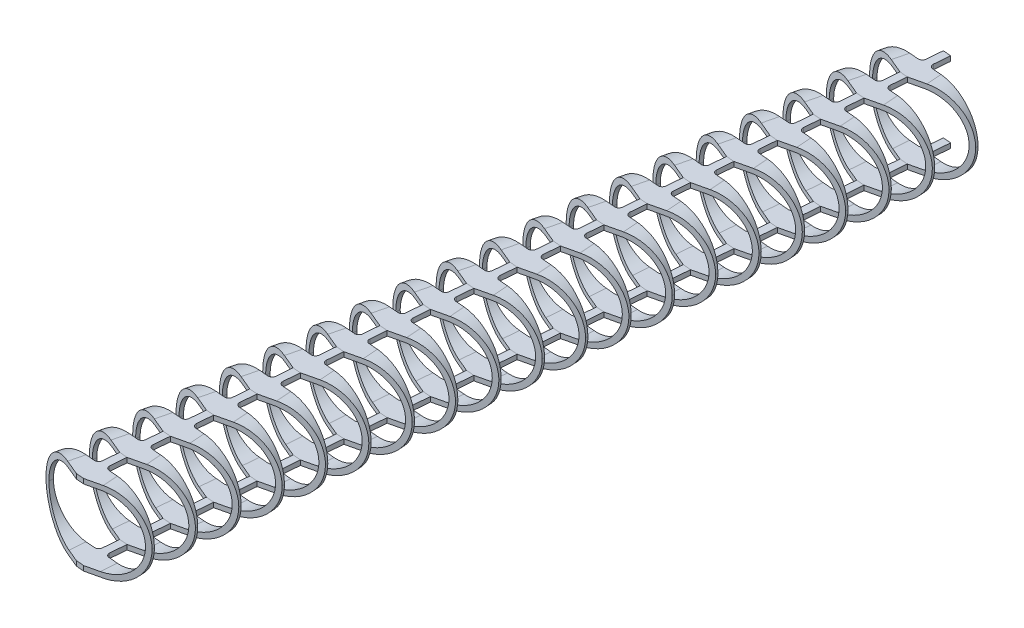
SolidWorks part; units mm, degrees
material "Rubber"
ref_plane "Front Plane" through (0, 0, 0) normal (0, 0, 1) x (1, 0, 0)
ref_plane "Top Plane" through (0, 0, 0) normal (0, 1, 0) x (1, 0, 0)
ref_plane "Right Plane" through (0, 0, 0) normal (1, 0, 0) x (0, 0, -1)
sketch "Sketch1" plane through (0, 0, 0) normal (0, 1, 0) x (1, 0, 0)
  line L1 (41.8892, -69.2126) -> (74.5712, -31.3723) construction
  line L2 (74.5712, -31.3723) -> (78.7696, 18.4511) construction
  line L3 (78.7696, 18.4511) -> (52.8806, 61.2268) construction
  line L4 (52.8806, 61.2268) -> (6.7931, 80.616) construction
  line L5 (6.7931, 80.616) -> (-41.8892, 69.2126) construction
  line L6 (-41.8892, 69.2126) -> (-74.5712, 31.3723) construction
  line L7 (-74.5712, 31.3723) -> (-78.7696, -18.4511) construction
  line L8 (-78.7696, -18.4511) -> (-52.8806, -61.2268) construction
  line L9 (-52.8806, -61.2268) -> (-6.7931, -80.616) construction
  line L10 (-6.7931, -80.616) -> (41.8892, -69.2126) construction
  line L11 (9.9647, -0.8397) -> (76.6704, -6.4606)
  line L12 (74.5712, -31.3723) -> (9.2175, -3.8778)
  line L13 (9.2175, -3.8778) -> (9.9647, -0.8397)
  line L18 (79.5535, -31.7922) -> (83.7519, 18.0313) construction
  line L19 (76.6704, -6.4606) -> (78.7696, 18.4511)
  line L20 (78.7696, 18.4511) -> (88.7342, 17.6114)
  line L21 (74.5712, -31.3723) -> (84.5359, -32.212)
  line L22 (86.6351, -7.3003) -> (88.7342, 17.6114)
  line L23 (84.5359, -32.212) -> (153.569, -16.0416)
  line L24 (153.569, -16.0416) -> (153.3407, -12.9213)
  line L25 (153.3407, -12.9213) -> (86.6351, -7.3003)
  line L26 (76.6704, -6.4606) -> (86.6351, -7.3003) construction
  circle A0 centre (0, 0) radius 10 construction
  circle A2 centre (0, 0) radius 76.9421 construction
  dimension "D1" = 20
  dimension "D2" = 50
  dimension "D3" = 76.9421
extrude "Boss-Extrude2" add sketch "Sketch1" along normal blind 100
fillet "Fillet1" radius 50 4 edges at (9.5911, 100, 2.3588) (9.5911, 0, 2.3588) (153.4549, 0, 14.4814) (153.4549, 100, 14.4814)
fillet "Fillet2" radius 5 2 edges at (76.6704, 50, 6.4606) (86.6351, 50, 7.3003)
sketch "Sketch8" plane through (0, 0, 0) normal (0.084, 0, -0.9965) x (-0.9965, 0, -0.084)
  line L0 (-71.9421, 100) -> (-91.9421, 100) construction
  line L1 (-81.9421, 100) -> (-81.9421, 0) construction
  line L2 (-97.9421, 94) -> (-65.9421, 94)
  line L3 (-65.9421, 6) -> (-97.9421, 6)
  line L26 (-60.6233, 94) -> (-65.9421, 94)
  line L27 (-65.9421, 94) -> (-65.9421, 6)
  line L28 (-65.9421, 6) -> (-60.6233, 6)
  line L29 (-60.6233, 94) -> (-65.9421, 94)
  line L31 (-65.9421, 6) -> (-60.6233, 6)
  line L35 (-103.2609, 6) -> (-97.9421, 6)
  line L36 (-97.9421, 6) -> (-97.9421, 94)
  line L37 (-97.9421, 94) -> (-103.2609, 94)
  line L38 (-103.2609, 6) -> (-97.9421, 6)
  line L40 (-97.9421, 94) -> (-103.2609, 94)
  spline S0 degree 3 poles (-1167.3923, 3837.039) (-480.5269, 705.4147) (-201.9731, -22.3402) (-50.5717, 7.1072) (-49.1672, 7.4506) (-46.3819, 8.2764) (-44.9956, 8.7616) (-40.9575, 10.3993) (-38.4016, 11.7367) (-34.7705, 14.1083) (-33.5942, 14.9602) (-31.3123, 16.7917) (-30.2259, 17.7559) (-27.126, 20.7889) (-25.27, 22.9968) (-22.809, 26.5942) (-22.0407, 27.8467) (-20.6474, 30.3952) (-19.3888, 32.9977) (-18.3948, 35.7064) (-17.7498, 37.7782) (-17.5516, 38.4755) (-17.1892, 39.8838) (-17.0248, 40.5962) (20.8316, 225.9233) (-1153.7583, 538.5496) (-3883.4737, 1015.3924) knots -6.495019 -6.495019 -6.495019 -6.495019 0.125 0.125 0.1875 0.1875 0.25 0.25 0.375 0.375 0.4375 0.4375 0.5 0.5 0.625 0.625 0.6875 0.6875 0.75 0.8125 0.8125 0.84375 0.84375 0.875 0.875 8.929608 8.929608 8.929608 8.929608 only from (-60.6233, 6) to (-16, 50)
  spline S1 degree 3 poles (-3850.2068, -1047.6989) (-700.7376, -359.2624) (12.651, -86.8768) (-17.1536, 60.0441) (-17.5112, 61.4461) (-18.1559, 63.5305) (-18.3896, 64.224) (-18.8905, 65.5954) (-19.1572, 66.2722) (-20.5702, 69.6118) (-21.9524, 72.1439) (-23.9915, 75.1366) (-24.4151, 75.7264) (-25.2941, 76.8884) (-25.7506, 77.4617) (-27.1543, 79.1374) (-28.1386, 80.2004) (-31.2327, 83.232) (-33.4822, 85.0448) (-36.533, 87.0442) (-37.1551, 87.4304) (-38.4097, 88.1675) (-39.044, 88.5196) (-40.9672, 89.5272) (-43.5859, 90.7414) (-46.312, 91.7003) (-48.3973, 92.3224) (-49.0993, 92.5135) (-50.517, 92.8627) (-51.2313, 93.0204) (-231.643, 128.2853) (-539.1448, -934.7881) (-1052.4637, -3766.3996) knots -6.30639 -6.30639 -6.30639 -6.30639 0.125 0.125 0.1875 0.1875 0.21875 0.21875 0.25 0.25 0.375 0.375 0.40625 0.40625 0.4375 0.4375 0.5 0.5 0.625 0.625 0.65625 0.65625 0.6875 0.6875 0.75 0.8125 0.8125 0.84375 0.84375 0.875 0.875 8.729297 8.729297 8.729297 8.729297 only from (-16, 50) to (-60.6233, 94)
  spline S2 degree 3 poles (-60.6233, 6) (-57.6977, 6) (-54.8198, 6.281) (-50.5717, 7.1072) (-49.1672, 7.4506) (-46.3819, 8.2764) (-44.9956, 8.7616) (-40.9575, 10.3993) (-38.4016, 11.7367) (-34.7705, 14.1083) (-33.5942, 14.9602) (-31.3123, 16.7917) (-30.2259, 17.7559) (-27.126, 20.7889) (-25.27, 22.9968) (-22.809, 26.5942) (-22.0407, 27.8467) (-20.6474, 30.3952) (-19.3888, 32.9977) (-18.3948, 35.7064) (-17.7498, 37.7782) (-17.5516, 38.4755) (-17.1892, 39.8838) (-17.0248, 40.5962) (-16.2933, 44.1774) (-16, 47.0732) (-16, 50) knots 0 0 0 0 0.125 0.125 0.1875 0.1875 0.25 0.25 0.375 0.375 0.4375 0.4375 0.5 0.5 0.625 0.625 0.6875 0.6875 0.75 0.8125 0.8125 0.84375 0.84375 0.875 0.875 1 1 1 1
  spline S3 degree 3 poles (-16, 50) (-16, 52.926) (-16.2931, 55.802) (-17.1536, 60.0441) (-17.5112, 61.4461) (-18.1559, 63.5305) (-18.3896, 64.224) (-18.8905, 65.5954) (-19.1572, 66.2722) (-20.5702, 69.6118) (-21.9524, 72.1439) (-23.9915, 75.1366) (-24.4151, 75.7264) (-25.2941, 76.8884) (-25.7506, 77.4617) (-27.1543, 79.1374) (-28.1386, 80.2004) (-31.2327, 83.232) (-33.4822, 85.0448) (-36.533, 87.0442) (-37.1551, 87.4304) (-38.4097, 88.1675) (-39.044, 88.5196) (-40.9672, 89.5272) (-43.5859, 90.7414) (-46.312, 91.7003) (-48.3973, 92.3224) (-49.0993, 92.5135) (-50.517, 92.8627) (-51.2313, 93.0204) (-54.8061, 93.7191) (-57.6984, 94) (-60.6233, 94) knots 0 0 0 0 0.125 0.125 0.1875 0.1875 0.21875 0.21875 0.25 0.25 0.375 0.375 0.40625 0.40625 0.4375 0.4375 0.5 0.5 0.625 0.625 0.65625 0.65625 0.6875 0.6875 0.75 0.8125 0.8125 0.84375 0.84375 0.875 0.875 1 1 1 1
  spline S4 degree 3 poles (1003.5081, -3737.039) (316.6427, -605.4147) (38.0889, 122.3402) (-113.3125, 92.8928) (-114.7169, 92.5494) (-117.5023, 91.7236) (-118.8886, 91.2384) (-122.9267, 89.6007) (-125.4826, 88.2633) (-129.1137, 85.8917) (-130.29, 85.0398) (-132.5719, 83.2083) (-133.6583, 82.2441) (-136.7581, 79.2111) (-138.6142, 77.0032) (-141.0751, 73.4058) (-141.8435, 72.1533) (-143.2368, 69.6048) (-144.4954, 67.0023) (-145.4894, 64.2936) (-146.1344, 62.2218) (-146.3326, 61.5245) (-146.695, 60.1162) (-146.8594, 59.4038) (-184.7158, -125.9233) (989.8741, -438.5496) (3719.5895, -915.3924) knots -6.495019 -6.495019 -6.495019 -6.495019 0.125 0.125 0.1875 0.1875 0.25 0.25 0.375 0.375 0.4375 0.4375 0.5 0.5 0.625 0.625 0.6875 0.6875 0.75 0.8125 0.8125 0.84375 0.84375 0.875 0.875 8.929608 8.929608 8.929608 8.929608 only from (-103.2609, 94) to (-147.8842, 50)
  spline S5 degree 3 poles (3686.3226, 1147.6989) (536.8534, 459.2624) (-176.5351, 186.8768) (-146.7306, 39.9559) (-146.373, 38.5539) (-145.7283, 36.4695) (-145.4946, 35.776) (-144.9936, 34.4046) (-144.7269, 33.7278) (-143.314, 30.3882) (-141.9318, 27.8561) (-139.8927, 24.8634) (-139.4691, 24.2736) (-138.5901, 23.1116) (-138.1336, 22.5383) (-136.7299, 20.8626) (-135.7455, 19.7996) (-132.6514, 16.768) (-130.402, 14.9552) (-127.3511, 12.9558) (-126.7291, 12.5696) (-125.4744, 11.8325) (-124.8402, 11.4804) (-122.9169, 10.4728) (-120.2982, 9.2586) (-117.5722, 8.2997) (-115.4869, 7.6776) (-114.7849, 7.4865) (-113.3671, 7.1373) (-112.6529, 6.9796) (67.7589, -28.2853) (375.2606, 1034.7881) (888.5795, 3866.3996) knots -6.30639 -6.30639 -6.30639 -6.30639 0.125 0.125 0.1875 0.1875 0.21875 0.21875 0.25 0.25 0.375 0.375 0.40625 0.40625 0.4375 0.4375 0.5 0.5 0.625 0.625 0.65625 0.65625 0.6875 0.6875 0.75 0.8125 0.8125 0.84375 0.84375 0.875 0.875 8.729297 8.729297 8.729297 8.729297 only from (-147.8842, 50) to (-103.2609, 6)
  spline S6 degree 3 poles (-103.2609, 94) (-106.1865, 94) (-109.0644, 93.719) (-113.3125, 92.8928) (-114.7169, 92.5494) (-117.5023, 91.7236) (-118.8886, 91.2384) (-122.9267, 89.6007) (-125.4826, 88.2633) (-129.1137, 85.8917) (-130.29, 85.0398) (-132.5719, 83.2083) (-133.6583, 82.2441) (-136.7581, 79.2111) (-138.6142, 77.0032) (-141.0751, 73.4058) (-141.8435, 72.1533) (-143.2368, 69.6048) (-144.4954, 67.0023) (-145.4894, 64.2936) (-146.1344, 62.2218) (-146.3326, 61.5245) (-146.695, 60.1162) (-146.8594, 59.4038) (-147.5909, 55.8226) (-147.8842, 52.9268) (-147.8842, 50) knots 0 0 0 0 0.125 0.125 0.1875 0.1875 0.25 0.25 0.375 0.375 0.4375 0.4375 0.5 0.5 0.625 0.625 0.6875 0.6875 0.75 0.8125 0.8125 0.84375 0.84375 0.875 0.875 1 1 1 1
  spline S7 degree 3 poles (-147.8842, 50) (-147.8842, 47.074) (-147.5911, 44.198) (-146.7306, 39.9559) (-146.373, 38.5539) (-145.7283, 36.4695) (-145.4946, 35.776) (-144.9936, 34.4046) (-144.7269, 33.7278) (-143.314, 30.3882) (-141.9318, 27.8561) (-139.8927, 24.8634) (-139.4691, 24.2736) (-138.5901, 23.1116) (-138.1336, 22.5383) (-136.7299, 20.8626) (-135.7455, 19.7996) (-132.6514, 16.768) (-130.402, 14.9552) (-127.3511, 12.9558) (-126.7291, 12.5696) (-125.4744, 11.8325) (-124.8402, 11.4804) (-122.9169, 10.4728) (-120.2982, 9.2586) (-117.5722, 8.2997) (-115.4869, 7.6776) (-114.7849, 7.4865) (-113.3671, 7.1373) (-112.6529, 6.9796) (-109.078, 6.2809) (-106.1858, 6) (-103.2609, 6) knots 0 0 0 0 0.125 0.125 0.1875 0.1875 0.21875 0.21875 0.25 0.25 0.375 0.375 0.40625 0.40625 0.4375 0.4375 0.5 0.5 0.625 0.625 0.65625 0.65625 0.6875 0.6875 0.75 0.8125 0.8125 0.84375 0.84375 0.875 0.875 1 1 1 1
  dimension "D1" = 6
  dimension "D2" = 6
extrude "Cut-Extrude3" cut sketch "Sketch8" against normal blind 47 and the other way blind 47
pattern_linear "LPattern2" count 20 spacing 50 along (0.084, 0, -0.9965) of bodies 125
